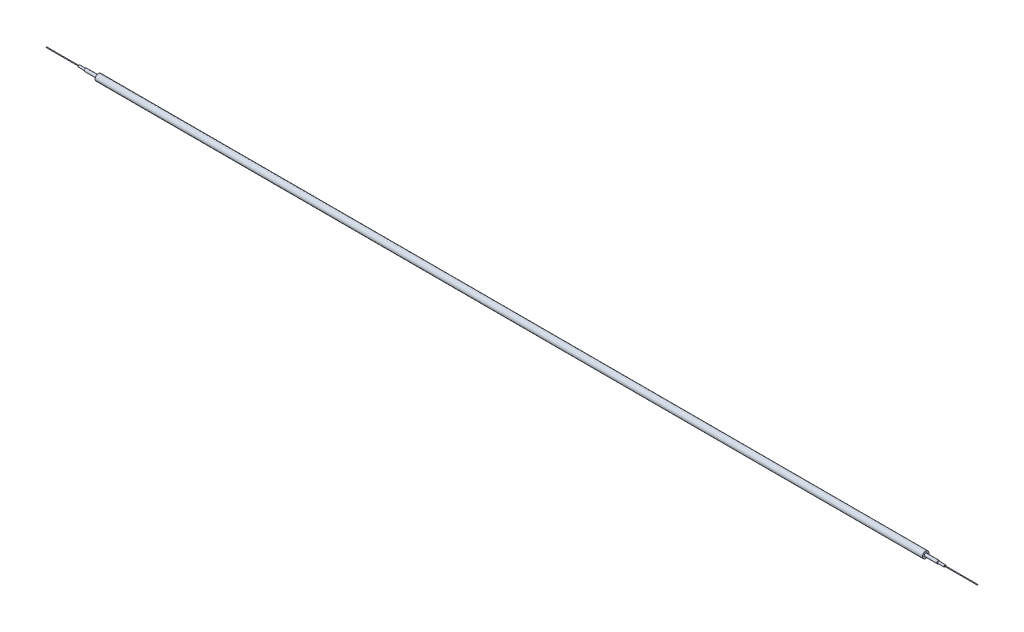
SolidWorks part; units mm, degrees
ref_plane "Front" through (0, 0, 0) normal (0, 0, 1) x (1, 0, 0)
ref_plane "Top" through (0, 0, 0) normal (0, 1, 0) x (1, 0, 0)
ref_plane "Right" through (0, 0, 0) normal (1, 0, 0) x (0, 0, -1)
sketch "Sketch3" plane through (0, 0, 0) normal (1, 0, 0) x (0, 0, -1)
  circle A0 centre (0, 0) radius 12.7
  dimension "D1" = 25.4
extrude "Boss-Extrude1" add sketch "Sketch3" along normal blind 3230.88
sketch "Sketch4" plane through (3230.88, 0, 0) normal (1, 0, 0) x (0, 0, -1)
  circle A0 centre (0, 0) radius 5.4991
  dimension "D1" = 10.9982
extrude "Boss-Extrude2" add sketch "Sketch4" along normal blind 50.8
sketch "Sketch5" plane through (0, 0, 0) normal (-1, 0, 0) x (0, 0, 1)
  circle A0 centre (0, 0) radius 5.4991
  dimension "D1" = 10.9982
extrude "Boss-Extrude3" add sketch "Sketch5" along normal blind 50.8
sketch "Sketch6" plane through (-50.8, 0, 0) normal (-1, 0, 0) x (0, 0, 1)
  circle A0 centre (0, 0) radius 3.81
  dimension "D1" = 7.62
extrude "Boss-Extrude4" add sketch "Sketch6" along normal blind 25.4
sketch "Sketch7" plane through (3281.68, 0, 0) normal (1, 0, 0) x (0, 0, -1)
  circle A0 centre (0, 0) radius 3.81
  dimension "D1" = 7.62
extrude "Boss-Extrude5" add sketch "Sketch7" along normal blind 25.4
chamfer "Chamfer1" distance 1.27 angle 45 4 edges at (-76.2, 0, 3.81) (-50.8, 0, 5.4991) (3307.08, 0, -3.81) (3281.68, 0, -5.4991)
sketch "Sketch8" plane through (-76.2, 0, 0) normal (-1, 0, 0) x (0, 0, 1)
  circle A0 centre (0, 0) radius 1.27
  dimension "D1" = 2.54
extrude "Boss-Extrude6" add sketch "Sketch8" along normal blind 127
sketch "Sketch9" plane through (3307.08, 0, 0) normal (1, 0, 0) x (0, 0, -1)
  circle A0 centre (0, 0) radius 1.27
  dimension "D1" = 2.54
extrude "Boss-Extrude7" add sketch "Sketch9" along normal blind 127
sketch "Sketch10" [suppressed] plane through (3434.08, 0, 0) normal (1, 0, 0) x (0, 0, -1)
  line L0 (-1.27, 0) -> (-53.975, 0) construction
  line L5 (-323.85, 1.27) -> (215.9, 1.27)
  line L6 (-323.85, 1.27) -> (-323.85, -1.27)
  line L7 (-323.85, -1.27) -> (215.9, -1.27)
  line L8 (215.9, 1.27) -> (215.9, -1.27)
  line L9 (-323.85, 1.27) -> (215.9, -1.27) construction
  line L10 (-323.85, -1.27) -> (215.9, 1.27) construction
  circle A1 centre (0, 0) radius 1.27 construction
  point P0 (-53.975, 0)
  dimension "D1" = 2.54
  dimension "D2" = 215.9
  dimension "D3" = 323.85
extrude "Boss-Extrude8" [suppressed] add sketch "Sketch10" along normal blind 5.08
sketch "Sketch11" [suppressed] plane through (3439.16, 0, 0) normal (1, 0, 0) x (0, 0, -1)
  circle A0 centre (0, 0) radius 1.27
  dimension "D1" = 2.54
extrude "Boss-Extrude9" [suppressed] add sketch "Sketch11" along normal blind 304.8
